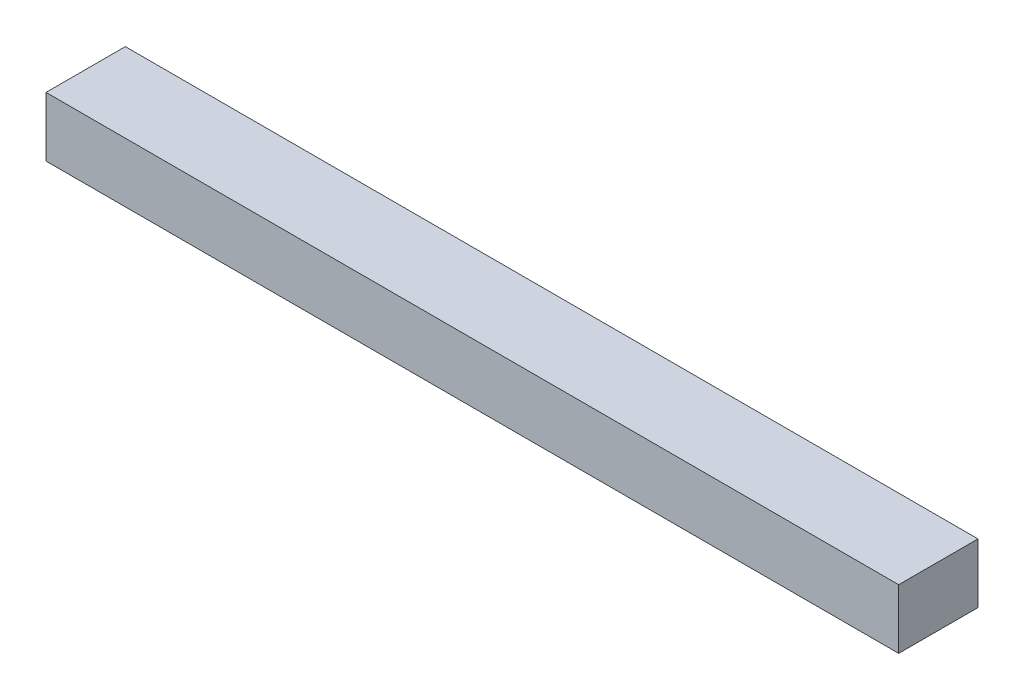
SolidWorks part; units mm, degrees
material "Maple"
ref_plane "Front Plane" through (0, 0, 0) normal (0, 0, 1) x (1, 0, 0)
ref_plane "Top Plane" through (0, 0, 0) normal (0, 1, 0) x (1, 0, 0)
ref_plane "Right Plane" through (0, 0, 0) normal (1, 0, 0) x (0, 0, -1)
sketch "Sketch1" plane through (0, 0, 0) normal (0, 1, 0) x (1, 0, 0)
  line L1 (0, 0) -> (86, 0)
  line L2 (0, 0) -> (0, 8)
  line L3 (0, 8) -> (86, 8)
  line L4 (86, 0) -> (86, 8)
  dimension "D2" = 8
extrude "Boss-Extrude1" add sketch "Sketch1" along normal blind 6
ref_plane "Plane1" through (0, 3, 0) normal (0, 1, 0) x (1, 0, 0)
